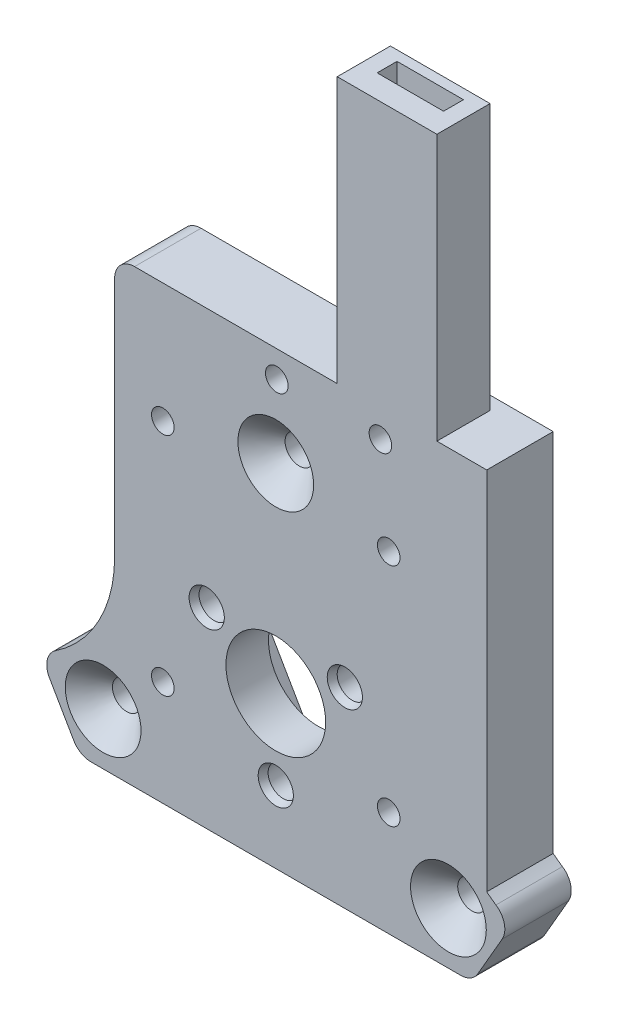
SolidWorks part; units mm, degrees
note: '?' marks a value the reader was unsure of.
other "tool plate"
material "PET"
ref_plane "Front" through (0, 0, 0) normal (0, 0, 1) x (1, 0, 0)
ref_plane "Top" through (0, 0, 0) normal (0, 1, 0) x (1, 0, 0)
ref_plane "Right" through (0, 0, 0) normal (1, 0, 0) x (0, 0, -1)
sketch "Sketch1" plane through (0, 0, 0) normal (0, 0, 1) x (1, 0, 0)
  line L0 (0, 0) -> (0, 30) construction
  line L1 (0, 0) -> (-25.9808, -15) construction
  line L2 (0, 0) -> (25.9808, -15) construction
  line L4 (-6, -1) -> (6, -1)
  line L5 (-6, -1) -> (-6, 1)
  line L6 (-6, 1) -> (6, 1)
  line L7 (6, -1) -> (6, 1)
  line L8 (-6, -1) -> (6, 1) construction
  line L9 (-6, 1) -> (6, -1) construction
  circle A0 centre (0, 0) radius 2.5
  circle A1 centre (0, 30) radius 4
  circle A2 centre (25.9808, -15) radius 4
  circle A3 centre (-25.9808, -15) radius 4
  dimension "D4" = 5
  dimension "D7" = 8
  dimension "D1" = 30
  dimension "D2" = 120
  dimension "D3" = 120
  dimension "D5" = 12
  dimension "D6" = 2
ref_plane "Plane1" through (0, 30, 0) normal (0, 1, 0) x (1, 0, 0)
sketch "Sketch10" plane through (0, 30, 0) normal (0, 1, 0) x (1, 0, 0)
  line L0 (0, 7.5) -> (0, 0) construction
  line L1 (-6, 0) -> (6, 0) construction
  circle A0 centre (0, 3.5) radius 4
  dimension "D1" = 8
  dimension "D2" = 7.5
sketch "Sketch2" plane through (0, 0, 0) normal (0, 0, 1) x (1, 0, 0)
  line L0 (0, 0) -> (0, 30) construction
  line L1 (0, 0) -> (0, 30) construction
  line L2 (-24.25, 45) -> (24.25, 45)
  line L3 (24.25, 45) -> (24.25, -5.9178)
  line L4 (-24.25, 45) -> (-24.25, -5.9178)
  line L5 (24.25, -5.9178) -> (35.5429, -12.4378)
  line L6 (35.5429, -12.4378) -> (29.5429, -22.8301)
  line L7 (29.5429, -22.8301) -> (-29.5429, -22.8301)
  line L8 (0, 0) -> (25.9808, -15) construction
  line L9 (32.0429, -18.5) -> (25.9808, -15) construction
  line L10 (-35.5429, -12.4378) -> (-29.5429, -22.8301)
  line L11 (-24.25, -5.9178) -> (-35.5429, -12.4378)
  circle A0 centre (25.9808, -15) radius 4 construction
  circle A1 centre (0, 0) radius 7.5
  point P8 (0, 45)
  point P19 (0, -22.8301)
  dimension "D3" = 7
  dimension "D5" = 15
  dimension "D1" = 24.25
  dimension "D2" = 15
  dimension "D4" = 12
  dimension "D6" = 5
extrude "Boss-Extrude1" add sketch "Sketch2" along normal blind 10
hole_wizard "CSK for M4 Flat Head Machine Screw1" positions "Sketch8" profile "Sketch9" countersink size "M4" standard "ANSI Metric"
sketch "Sketch8" plane through (0, 0, 10) normal (0, 0, 1) x (1, 0, 0)
  point P0 (-25.9808, -15)
  point P3 (0, 30)
  point P6 (25.9808, -15)
sketch "Sketch9" plane through (-25.9808, -15, 10) normal (1, 0, 0) x (0, -1, 0)
  line L0 (0, 0) -> (0, 11.2909)
  line L1 (0, 11.2909) -> (2.15, 9.999)
  line L2 (2.15, 9.999) -> (2.15, 3.55)
  line L3 (2.15, 3.55) -> (5.7, 0)
  line L5 (5.7, 0) -> (0, 0)
  line L6 (-2.15, 3.55) -> (-5.7, 0) construction
  line L10 (0, 11.2909) -> (-2.15, 9.999) construction
  line L11 (0, -6.35) -> (0, 107.95) construction
  dimension "Hole Dia." = 4.3
  dimension "Hole Depth" = 9.999
  dimension "Near C'Sink Dia." = 11.4
  dimension "Near C'Sink Angle" = 90
  dimension "Drill Angle" = 118
fillet "Fillet1" radius 20 2 edges at (-24.25, -5.9178, 5) (24.25, -5.9178, 5)
sketch "Sketch44" plane through (0, 0, 0) normal (0, 0, -1) x (-1, 0, 0)
  line L0 (10.3923, 10) -> (-10.3923, 10)
  line L1 (0, -20) -> (17.3205, 10) construction
  line L2 (17.3205, 10) -> (-17.3205, 10) construction
  line L3 (-17.3205, 10) -> (0, -20) construction
  line L4 (-13.8564, 4) -> (-3.4641, -14)
  line L5 (3.4641, -14) -> (13.8564, 4)
  line L6 (-17.3205, 10) -> (0, -20) construction
  line L7 (0, -20) -> (17.3205, 10) construction
  line L8 (17.3205, 10) -> (-17.3205, 10) construction
  circle A0 centre (0, 0) radius 10 construction
  arc A1 (-3.4641, -14) -> (3.4641, -14) centre (0, -12) ccw
  arc A2 (10.3923, 10) -> (13.8564, 4) centre (10.3923, 6) cw
  arc A3 (-10.3923, 10) -> (-13.8564, 4) centre (-10.3923, 6) ccw
  dimension "D1" = 20
  dimension "D3" = 4
  dimension "D2" = 0
extrude "v-groove cutout" cut sketch "Sketch44" against normal blind 3.6
sketch "Sketch13" plane through (0, 0, 0) normal (0, 0, -1) x (-1, 0, 0)
  circle A0 centre (-10.3923, 6) radius 2.25
  circle A1 centre (10.3923, 6) radius 2.25
  circle A2 centre (0, -12) radius 2.25
  arc A3 (-10.3923, 10) -> (-13.8564, 4) centre (-10.3923, 6) ccw construction
  arc A4 (13.8564, 4) -> (10.3923, 10) centre (10.3923, 6) ccw construction
  arc A5 (-3.4641, -14) -> (3.4641, -14) centre (0, -12) ccw construction
  dimension "D1" = 4.5
extrude "standard tapered insert cutout" cut sketch "Sketch13" against normal through all and the other way through all
chamfer "taper for inserts" distance 0.4 angle 70 3 edges at (-2.25, -12, 10) (8.1423, 6, 10) (-12.6423, 6, 10) first distance on face at (8.1423, 6, 10)
other "Move Face1" flip direction yes face at (-8.6603, -5, 1.8) face at (0, -15, 1.8) face at (8.6603, -5, 1.8) face at (12.9904, 7.5, 1.8) face at (-12.9904, 7.5, 1.8) face at (0, 10, 1.8) parameters "D1"=0.5
ref_axis "Axis2" through (0, 30, 0) along (0, 0, 1)?
ref_plane "Plane5" through (0, 30, 0) normal (0, 1, 0) x (1, 0, 0)
sketch "Sketch46" plane through (0, 30, 0) normal (0, 1, 0) x (1, 0, 0)
  line L0 (0, 0) -> (0, 0.3) construction
  line L1 (0, 5.3) -> (0, -4.7)
  line L2 (0, 7.5) -> (0, 0) construction
  circle A0 centre (0, 0.3) radius 5 construction
  arc A1 (0, -4.7) -> (0, 5.3) centre (0, 0.3) cw
  dimension "D1" = 10
  dimension "D2" = 3.2
revolve "tool ball cutout" cut sketch "Sketch46" angle 360 about L0
pattern_circular "CirPattern2" count 3 over 360 about axis through (0, 0, 0) along (0, 0, 1) of "tool ball cutout"
fillet "Fillet2" radius 3 6 edges at (24.25, 45, 5) (-24.25, 45, 5) (-29.5429, -22.8301, 5) (-35.5429, -12.4378, 5) (29.5429, -22.8301, 5) (35.5429, -12.4378, 5)
sketch "Sketch47" plane through (0, 0, 0) normal (0, 0, -1) x (-1, 0, 0)
  line L0 (0, 0) -> (0, 42.2664) construction
  line L1 (-17, 42.2664) -> (-17, -19.1503) construction
  line L2 (17, 36.2499) -> (17, -22.2786) construction
  line L3 (-17, 27) -> (17, 27) construction
  line L4 (-17, -7) -> (17, -7) construction
  line L5 (-21.25, 45) -> (21.25, 45) construction
  circle A0 centre (-17, 27) radius 1.7
  circle A1 centre (17, 27) radius 1.7
  circle A2 centre (17, -7) radius 1.7
  circle A3 centre (-17, -7) radius 1.7
  dimension "D5" = 3.4
  dimension "D6" = 3.4
  dimension "D7" = 3.4
  dimension "D8" = 3.4
  dimension "D1" = 34
  dimension "D2" = 17
  dimension "D3" = 34
  dimension "D4" = 18
extrude "Cut-Extrude1" cut sketch "Sketch47" against normal through all
sketch "Sketch49" plane through (0, 45, 0) normal (0, 1, 0) x (1, 0, 0)
  line L0 (21.25, 0) -> (-21.25, 0) construction
  line L1 (9.25, -10) -> (24.25, -10)
  line L2 (9.25, -10) -> (9.25, 0)
  line L3 (9.25, 0) -> (24.25, 0)
  line L4 (24.25, -10) -> (24.25, 0)
  line L5 (24.25, 0) -> (24.25, -10) construction
  line L6 (11.75, -3.5) -> (21.75, -3.5)
  line L7 (11.75, -3.5) -> (11.75, -6.5)
  line L8 (11.75, -6.5) -> (21.75, -6.5)
  line L9 (21.75, -3.5) -> (21.75, -6.5)
  dimension "D1" = 15
  dimension "D2" = 2.5
  dimension "D3" = 10
  dimension "D4" = 3
  dimension "D5" = 3.5
extrude "Boss-Extrude2" add sketch "Sketch49" along normal blind 40
chamfer "Chamfer1" distance 2 angle 45 4 edges at (15.3, -7, 0) (-18.7, -7, 0) (-18.7, 27, 0) (15.3, 27, 0)
sketch "Sketch51" plane through (0, 45, 0) normal (0, -1, 0) x (1, 0, 0)
  line L1 (24.25, 10) -> (21.25, 10)
  line L2 (24.25, 10) -> (24.25, 0)
  line L3 (24.25, 0) -> (21.25, 0)
  line L4 (21.25, 10) -> (21.25, 0)
extrude "Boss-Extrude3" add sketch "Sketch51" along normal up to next
sketch "Sketch52" plane through (0, 0, 10) normal (0, 0, 1) x (1, 0, 0)
  line L0 (24.25, 45) -> (31.75, 45)
  line L1 (24.25, 5.6292) -> (24.25, 85) construction
  line L2 (31.75, 45) -> (31.75, -9.9833)
  line L3 (24.25, 45) -> (24.25, 5.6292)
  arc A0 (24.25, 5.6292) -> (33.1366, -10.9989) centre (44.25, 5.6292) ccw construction
  arc A1 (24.25, 5.6292) -> (31.75, -9.9833) centre (44.25, 5.6292) ccw
  dimension "D1" = 7.5
extrude "Boss-Extrude4" add sketch "Sketch52" against normal up to surface (10 mm away) up to face at (-0.2248, 11.4014, 0)
sketch "Sketch48" plane through (0, 0, 10) normal (0, 0, 1) x (1, 0, 0)
  line L0 (9.25, 45) -> (-21.25, 45) construction
  line L2 (15.7503, 41) -> (0.1503, 41) construction
  line L3 (-24.25, 42) -> (-24.25, 5.6292) construction
  circle A0 centre (0.1503, 41) radius 1.7
  circle A1 centre (15.7503, 41) radius 1.7
  dimension "D1" = 3.4
  dimension "D2" = 3.4
  dimension "D3" = 15.6
  dimension "D4" = 4
  dimension "D5" = 24.4003
extrude "Cut-Extrude2" cut sketch "Sketch48" against normal through all
chamfer "Chamfer4" distance 2 angle 45 2 edges at (1.8503, 41, 0) (17.4503, 41, 0)
chamfer "Chamfer3" distance 2 angle 45 3 edges at (9.25, 65, 0) (16.75, 85, 0) (24.25, 65, 0)
